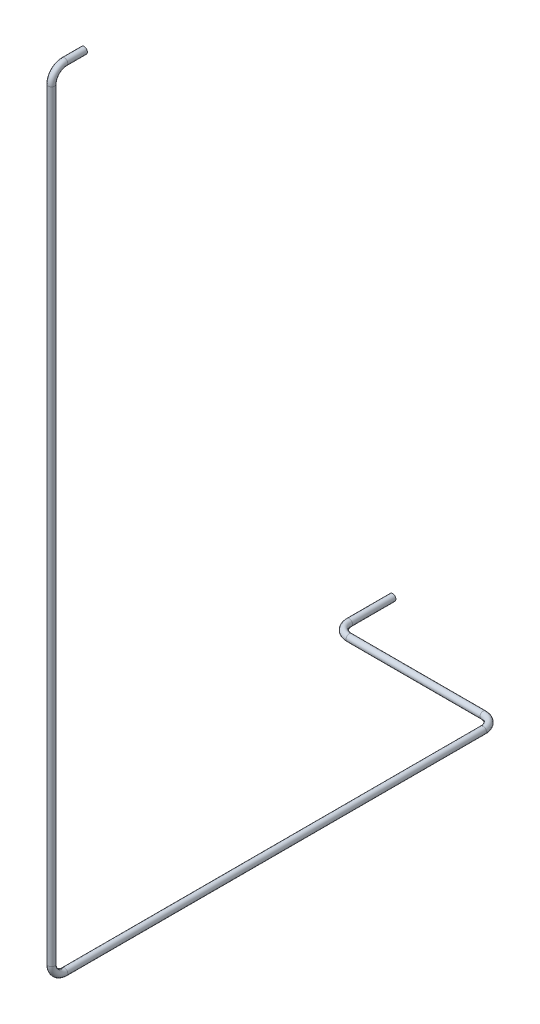
SolidWorks part; units mm, degrees
ref_plane "Plano frontal" through (0, 0, 0) normal (0, 0, 1) x (1, 0, 0)
ref_plane "Plano superior" through (0, 0, 0) normal (0, 1, 0) x (1, 0, 0)
ref_plane "Plano direito" through (0, 0, 0) normal (1, 0, 0) x (0, 0, -1)
sketch3d "3DSketch1"
  line L0 (-33126.1177, -14247.0136, 43090.4702) -> (-33126.1177, -14247.0136, 43140.4702) construction
  line L1 (-33126.1177, -14247.0136, 43140.4702) -> (-33126.1177, -14247.0136, 43230.4702)
  line L2 (-33126.1177, -14307.0136, 43290.4702) -> (-33126.1177, -17802.3318, 43290.4702)
  line L3 (-33126.1177, -17862.3318, 43230.4702) -> (-33126.1177, -17862.3318, 41310.1351)
  line L4 (-33186.1177, -17862.3318, 41250.1351) -> (-33800.3787, -17862.3318, 41250.1351)
  line L5 (-33860.3787, -17862.3318, 41190.1351) -> (-33860.3787, -17862.3318, 40991.2423)
  arc A0 (-33860.3787, -17862.3318, 41190.1351) -> (-33800.3787, -17862.3318, 41250.1351) centre (-33800.3787, -17862.3318, 41190.1351) ccw
  arc A2 (-33186.1177, -17862.3318, 41250.1351) -> (-33126.1177, -17862.3318, 41310.1351) centre (-33186.1177, -17862.3318, 41310.1351) ccw
  arc A3 (-33126.1177, -17862.3318, 43230.4702) -> (-33126.1177, -17802.3318, 43290.4702) centre (-33126.1177, -17802.3318, 43230.4702) ccw
  arc A4 (-33126.1177, -14307.0136, 43290.4702) -> (-33126.1177, -14247.0136, 43230.4702) centre (-33126.1177, -14307.0136, 43230.4702) ccw
  point P4 (0, 0, 0)
  point P7 (-33860.3787, -17862.3318, 40991.2423)
  point P10 (-33860.3787, -17862.3318, 41250.1351)
  point P12 (-33800.3787, -17802.3318, 41190.1351)
  point P13 (-34078.2843, -17862.3318, 41250.1351)
  point P17 (-33126.1177, -17862.3318, 41250.1351)
  point P18 (-33186.1177, -17922.3318, 41310.1351)
  point P21 (-33126.1177, -17862.3318, 43290.4702)
  point P22 (-33186.1177, -17802.3318, 43230.4702)
  point P25 (-33126.1177, -14247.0136, 43290.4702)
  point P26 (-33186.1177, -14307.0136, 43230.4702)
  dimension "D1" = 60
sweep "Sweep-Thin1" add path "3DSketch1" circular profile diameter 30 parameters "D1"=1, "D3"=30
